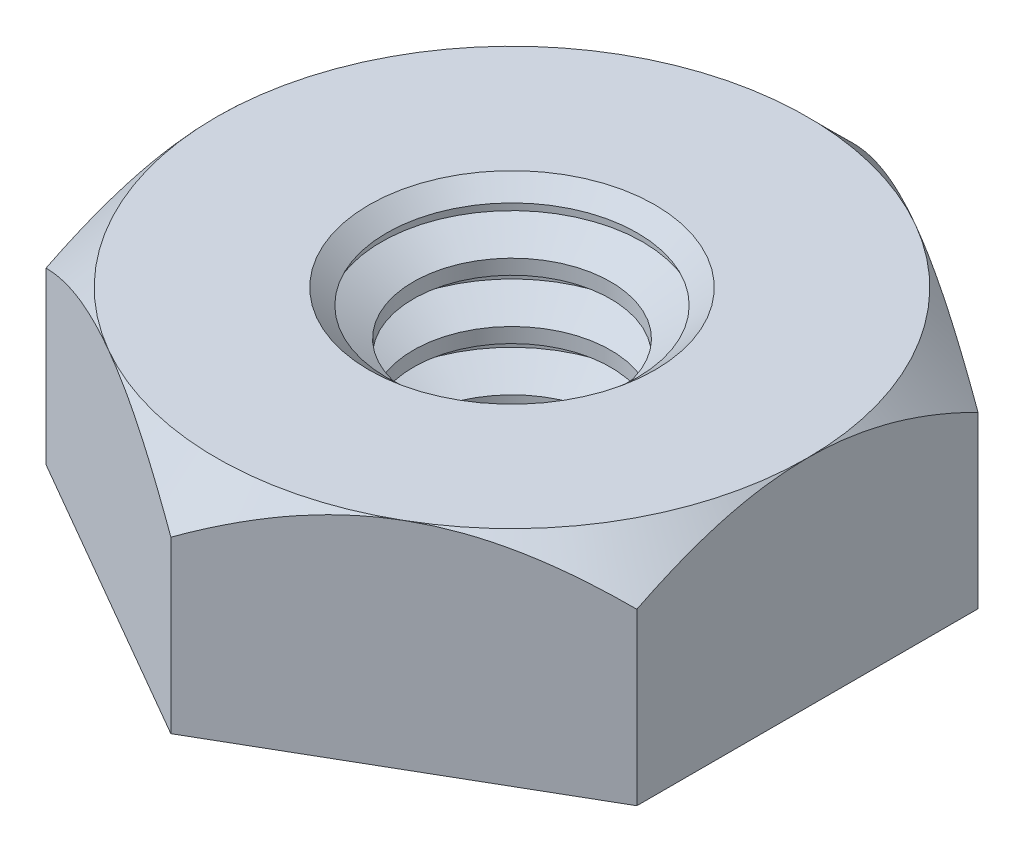
SolidWorks part; units mm, degrees
ref_plane "Front" through (0, 0, 0) normal (0, 0, 1) x (1, 0, 0)
ref_plane "Top" through (0, 0, 0) normal (0, 1, 0) x (1, 0, 0)
ref_plane "Right" through (0, 0, 0) normal (1, 0, 0) x (0, 0, -1)
sketch "Sketch1" plane through (0, 0, 0) normal (0, 1, 0) x (1, 0, 0)
  line L1 (0, 4.5754) -> (-3.9624, 2.2877)
  line L2 (-3.9624, 2.2877) -> (-3.9624, -2.2877)
  line L3 (-3.9624, -2.2877) -> (0, -4.5754)
  line L4 (0, -4.5754) -> (3.9624, -2.2877)
  line L5 (3.9624, -2.2877) -> (3.9624, 2.2877)
  line L6 (3.9624, 2.2877) -> (0, 4.5754)
  circle A0 centre (0, 0) radius 3.9624 construction
extrude "Extrude1" add sketch "Sketch1" along normal blind 2.8956
sketch "Sketch3" plane through (0, 0, 0) normal (1, 0, 0) x (0, 0, -1)
  line L0 (3.9624, 2.8956) -> (4.5754, 2.2826)
  line L1 (2.2877, 2.8956) -> (4.5754, 2.8956) construction
  line L2 (4.5754, 2.8956) -> (4.5754, 0) construction
  line L3 (4.5754, 2.2826) -> (4.5754, 2.8956)
  line L4 (4.5754, 2.8956) -> (3.9624, 2.8956)
  line L5 (0, 0.542) -> (0, -0.542) construction
  dimension "D1" = 45
revolve "Cut-Revolve2" cut sketch "Sketch3" angle 360 about L5
sketch "Sketch2" plane through (0, 0, 0) normal (0, 0, 1) x (1, 0, 0)
  line L0 (0, 1.6636) -> (0, -0.3796) construction
  line L1 (0, 2.8956) -> (1.323, 2.8956)
  line L3 (0, 2.8956) -> (3.9624, 2.8956) construction
  line L4 (0, 2.1018) -> (1.323, 2.1018)
  line L5 (1.323, 2.8956) -> (1.7526, 2.6476)
  line L6 (1.7526, 2.6476) -> (1.7526, 2.5483)
  line L7 (1.7526, 2.5483) -> (1.323, 2.3003)
  line L9 (1.323, 2.1018) -> (1.323, 2.3003)
  line L10 (0, 2.1018) -> (0, 2.8956)
  line L11 (1.323, 2.8956) -> (1.323, 2.3003) construction
  line L12 (1.7526, 2.5979) -> (1.323, 2.5979) construction
  dimension "D1" = 60
revolve "Cut-Revolve1" cut sketch "Sketch2" angle 360 about L0
pattern_linear "LPattern2" count 4 spacing 0.7937 along (0, -1, 0) of "Cut-Revolve1"
chamfer "Chamfer1" distance 0.5953 angle 41 1 edges at (0, 2.8956, 1.323) first distance on face at (0, 2.8956, 0)
equation "\"D5@Sketch2\"=\"Pitch@Sketch2\"/8"
equation "\"D2@Sketch2\"=\"Pitch@Sketch2\"/4"
equation "\"D3@LPattern2\"=\"Pitch@Sketch2\""
equation "\"D1@LPattern2\"=\"Height@Extrude1\"/\"Pitch@Sketch2\"+.5"
equation "\"D2@Sketch3\"=\"Hex Flats@Sketch1\""
equation "\"D1@Chamfer1\"=\"Pitch@Sketch2\"*.75"
